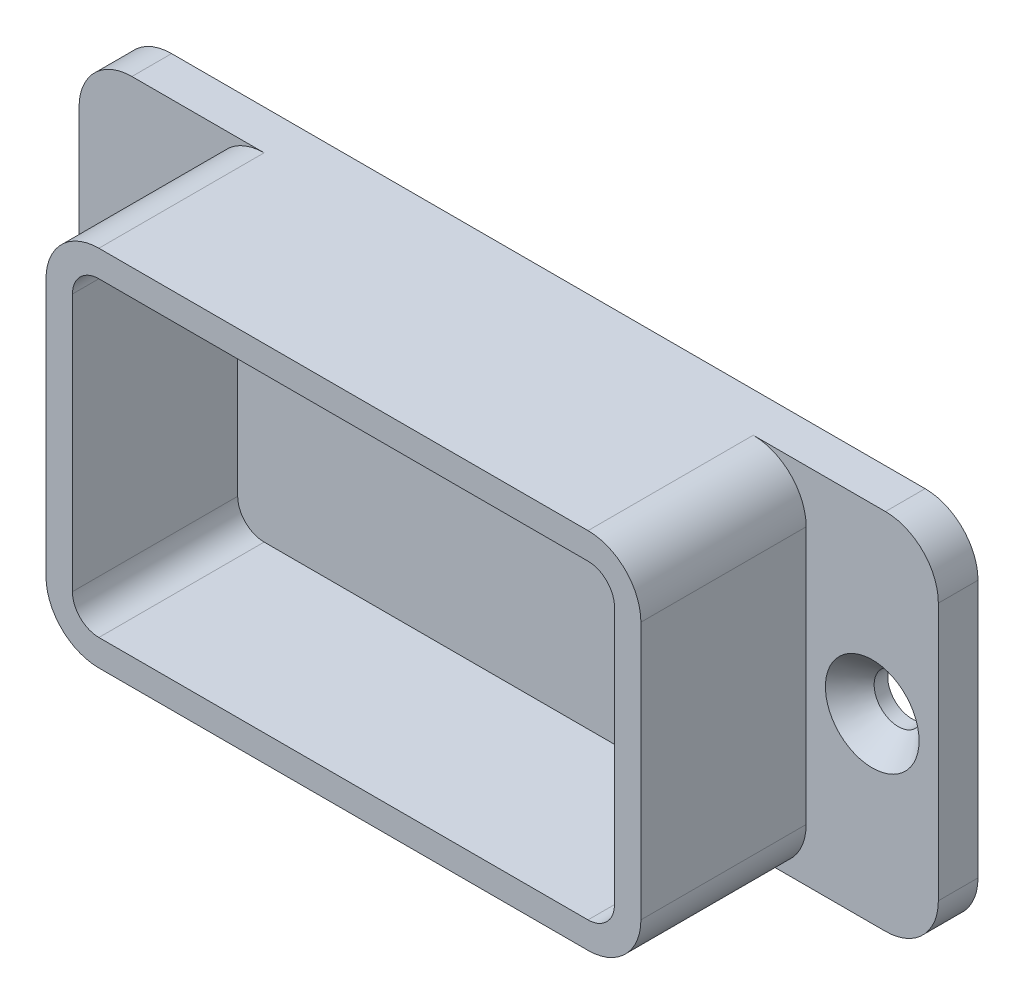
SolidWorks part; units mm, degrees
ref_plane "Front Plane" through (0, 0, 0) normal (0, 0, 1) x (1, 0, 0)
ref_plane "Top Plane" through (0, 0, 0) normal (0, 1, 0) x (1, 0, 0)
ref_plane "Right Plane" through (0, 0, 0) normal (1, 0, 0) x (0, 0, -1)
ref_plane "Bottom Plane" through (0, 0, -2.5) normal (0, 0, 1) x (1, 0, 0)
ref_plane "Top of Walls Plane" through (0, 0, 13) normal (0, 0, 1) x (1, 0, 0)
sketch "Walls Sketch" plane through (0, 0, -2.5) normal (0, 0, 1) x (1, 0, 0)
  line L1 (-20.5, -11.75) -> (20.5, -11.75)
  line L2 (-20.5, -11.75) -> (-20.5, 11.75)
  line L3 (-20.5, 11.75) -> (20.5, 11.75)
  line L4 (20.5, -11.75) -> (20.5, 11.75)
  line L5 (-20.5, -11.75) -> (20.5, 11.75) construction
  line L6 (-20.5, 11.75) -> (20.5, -11.75) construction
  line L7 (-22.5, -13.75) -> (22.5, -13.75)
  line L8 (-22.5, -13.75) -> (-22.5, 13.75)
  line L9 (-22.5, 13.75) -> (22.5, 13.75)
  line L10 (22.5, -13.75) -> (22.5, 13.75)
  line L11 (-22.5, -13.75) -> (22.5, 13.75) construction
  line L12 (-22.5, 13.75) -> (22.5, -13.75) construction
  point P0 (0, 0)
  point P6 (0, 0)
  dimension "D1" = 45
  dimension "D2" = 27.5
extrude "Walls Extrude" add sketch "Walls Sketch" along normal up to surface (15.5 mm away) up to plane "Top of Walls Plane"
sketch "Base Sketch" plane through (0, 0, -2.5) normal (0, 0, 1) x (1, 0, 0)
  line L0 (-22.5, -13.75) -> (22.5, -13.75) construction
  line L1 (-32.5, 13.75) -> (32.5, 13.75)
  line L2 (-32.5, 13.75) -> (-32.5, -13.75)
  line L3 (-32.5, -13.75) -> (32.5, -13.75)
  line L4 (32.5, 13.75) -> (32.5, -13.75)
  line L5 (22.5, 13.75) -> (-22.5, 13.75) construction
  line L6 (-22.5, 13.75) -> (-22.5, -13.75) construction
  line L7 (22.5, -13.75) -> (22.5, 13.75) construction
extrude "Base Extrude" add sketch "Base Sketch" along normal blind 3
hole_wizard "Mounting Holes" positions "Mounting Holes Position Sketch" profile "Mounting Holes Profile Sketch" countersink size "#6" standard "ANSI Inch" end condition through all
sketch "Mounting Holes Position Sketch" plane through (0, 0, 0.5) normal (0, 0, 1) x (1, 0, 0)
  line L0 (-32.5, 13.75) -> (-22.5, -13.75) construction
  line L2 (22.5, -13.75) -> (32.5, 13.75) construction
  line L3 (22.5, -13.75) -> (32.5, -13.75) construction
  point P0 (-27.5, 0)
  point P19 (27.5, 0)
sketch "Mounting Holes Profile Sketch" plane through (-27.5, 0, 0.5) normal (1, 0, 0) x (0, -1, 0)
  line L0 (0, 0) -> (0, 3)
  line L1 (0, 3) -> (1.8288, 3)
  line L2 (1.8288, 3) -> (1.8288, 1.9723)
  line L3 (1.8288, 1.9723) -> (3.5433, 0)
  line L5 (3.5433, 0) -> (0, 0)
  line L6 (-1.8288, 1.9723) -> (-3.5433, 0) construction
  line L11 (0, -6.35) -> (0, 107.95) construction
  dimension "Thru Hole Dia." = 3.6576
  dimension "Thru Hole Depth" = 3
  dimension "Near C'Sink Dia." = 7.0866
  dimension "Near C'Sink Angle" = 82
fillet "Tab Fillets" radius 4 4 edges at (32.5, 13.75, -1) (32.5, -13.75, -1) (-32.5, 13.75, -1) (-32.5, -13.75, -1)
fillet "Inside Corner Fillets" radius 2 4 edges at (-20.5, -11.75, 6.75) (20.5, -11.75, 6.75) (20.5, 11.75, 6.75) (-20.5, 11.75, 6.75)
fillet "Outside Corner Fillets" radius 4 4 edges at (-22.5, 13.75, 6.75) (22.5, 13.75, 6.75) (22.5, -13.75, 6.75) (-22.5, -13.75, 6.75)
